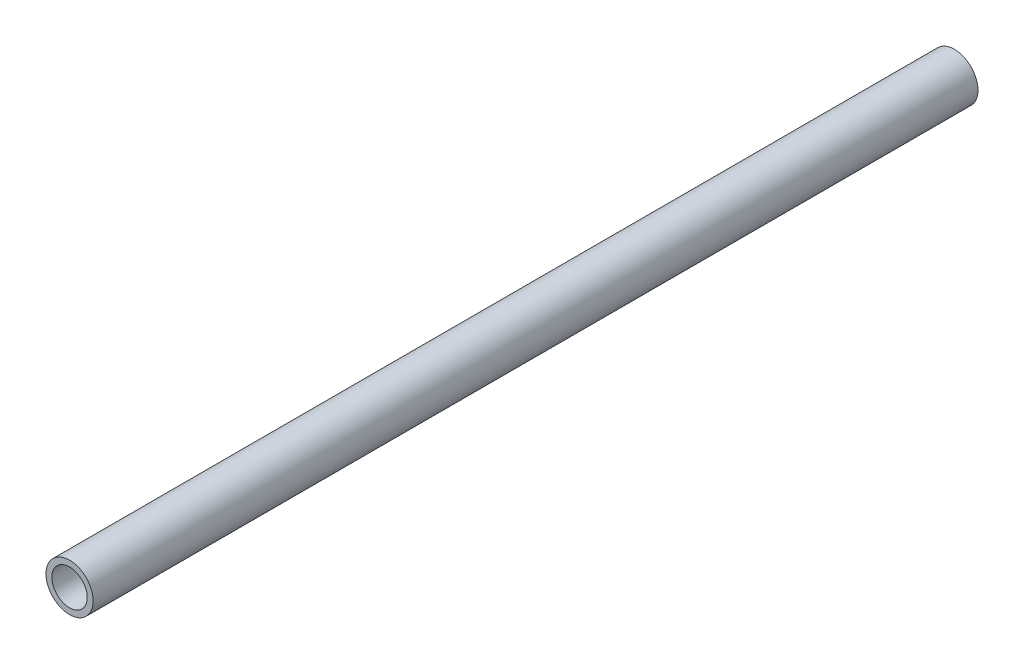
SolidWorks part; units mm, degrees
ref_plane "前视基准面" through (0, 0, 0) normal (0, 0, 1) x (1, 0, 0)
ref_plane "上视基准面" through (0, 0, 0) normal (0, 1, 0) x (1, 0, 0)
ref_plane "右视基准面" through (0, 0, 0) normal (1, 0, 0) x (0, 0, -1)
other "Configuration Table"
sketch "Sketch1" plane through (0, 0, 0) normal (0, 0, 1) x (1, 0, 0)
  circle A0 centre (0, 0) radius 20
  circle A1 centre (0, 0) radius 15
extrude "Boss-Extrude1" add sketch "Sketch1" along normal blind 750
ref_plane "bottom_face_ref" through (0, 0, 0) normal (0, 0, 1) x (1, 0, 0)
ref_plane "top_face_ref" through (0, 0, 750) normal (0, 0, 1) x (1, 0, 0)
sketch3d "3DSketch1"
  line L0 (0, 0, 0) -> (0, 0, 750) construction
ref_axis "central_axis" through (0, 0, 0) along (0, 0, 1)
